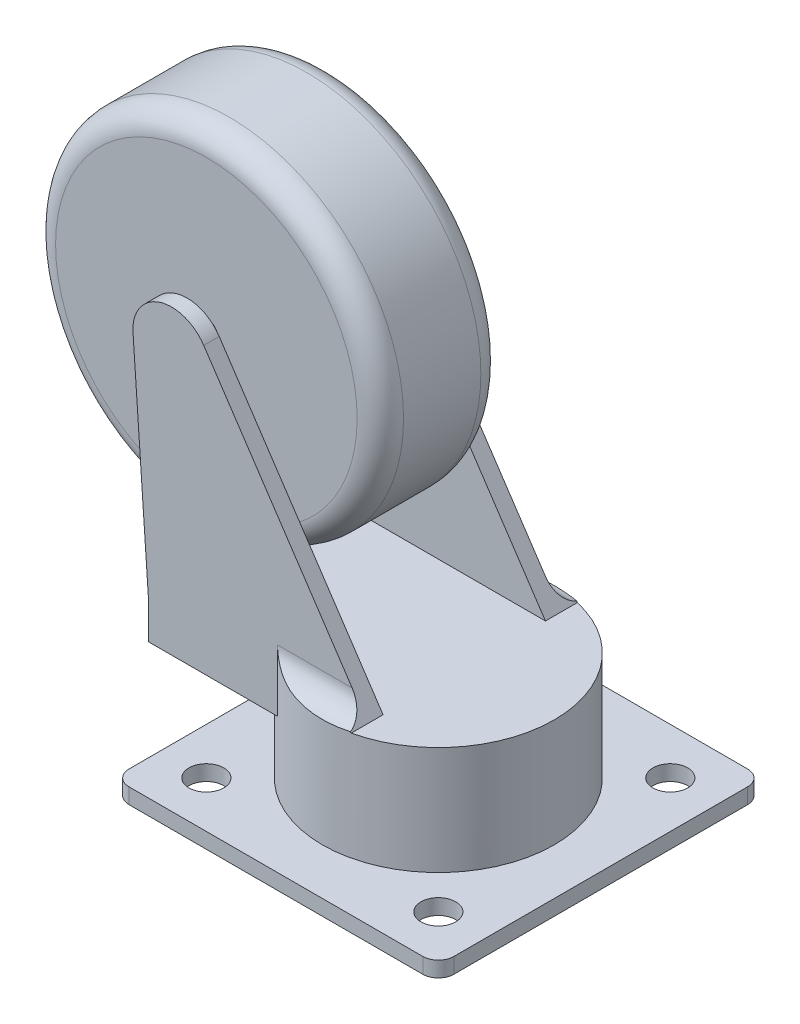
SolidWorks part; units mm, degrees
ref_plane "Front Plane" through (0, 0, 0) normal (0, 0, 1) x (1, 0, 0)
ref_plane "Top Plane" through (0, 0, 0) normal (0, 1, 0) x (1, 0, 0)
ref_plane "Right Plane" through (0, 0, 0) normal (1, 0, 0) x (0, 0, -1)
sketch "Sketch1" plane through (0, 0, 0) normal (0, 1, 0) x (1, 0, 0)
  line L0 (0, 21) -> (0, -21) construction
  line L1 (-19, 21) -> (19, 21)
  line L2 (-21, 19) -> (-21, -19)
  line L3 (-19, -21) -> (19, -21)
  line L4 (21, 19) -> (21, -19)
  line L5 (-21, 21) -> (21, -21) construction
  line L6 (-21, -21) -> (21, 21) construction
  line L7 (-21, 0) -> (21, 0) construction
  circle A0 centre (-15, 15) radius 2.25
  circle A2 centre (15, 15) radius 2.25
  circle A3 centre (15, -15) radius 2.25
  circle A4 centre (-15, -15) radius 2.25
  arc A5 (-21, -19) -> (-19, -21) centre (-19, -19) ccw
  arc A6 (19, -21) -> (21, -19) centre (19, -19) ccw
  arc A7 (19, 21) -> (21, 19) centre (19, 19) cw
  arc A8 (-19, 21) -> (-21, 19) centre (-19, 19) ccw
  point P0 (0, 0)
  dimension "D4" = 2
  dimension "D5" = 4.5
  dimension "D1" = 42
  dimension "D2" = 42
  dimension "D3" = 30
extrude "Boss-Extrude1" add sketch "Sketch1" along normal blind 2
sketch "Sketch2" plane through (0, 2, 0) normal (0, 1, 0) x (1, 0, 0)
  circle A0 centre (0, 0) radius 15
  dimension "D1" = 30
extrude "Boss-Extrude2" add sketch "Sketch2" along normal blind 9
sketch "Sketch3" plane through (0, 11, 0) normal (0, 1, 0) x (1, 0, 0)
  line L0 (0, 0) -> (-36.9933, 0) construction
  line L1 (-25, 12.5) -> (-8.2916, 12.5)
  line L2 (-25, -12.5) -> (-8.2916, -12.5)
  line L3 (-25, 12.5) -> (-25, -12.5)
  circle A0 centre (0, 0) radius 15 construction
  circle A1 centre (0, 0) radius 15 construction
  arc A2 (-8.2916, -12.5) -> (-8.2916, 12.5) centre (0, 0) ccw
  dimension "D1" = 25
  dimension "D2" = 25
extrude "Boss-Extrude3" add sketch "Sketch3" along normal blind 5
sketch "Sketch4" plane through (0, 0, 12.5) normal (0, 0, 1) x (1, 0, 0)
  line L0 (0, 0) -> (0, 48.0736) construction
  line L1 (0, 45) -> (-39.2355, 45) construction
  line L2 (-19, 0) -> (19, 0) construction
  line L3 (-25, 16) -> (-26.988, 44.6539)
  line L4 (3.3542, 16) -> (-17.8405, 47.7746)
  line L5 (15, 16) -> (-8.2916, 16) construction
  line L6 (-25, 16) -> (3.3542, 16)
  circle A0 centre (-22, 45) radius 1.5
  arc A1 (-17.8405, 47.7746) -> (-26.988, 44.6539) centre (-22, 45) ccw
  dimension "D3" = 3
  dimension "D4" = 10
  dimension "D1" = 45
  dimension "D2" = 22
extrude "Boss-Extrude4" add sketch "Sketch4" against normal blind 2
mirror "Mirror1" about plane through (0, 0, 0) normal (0, 0, 1) of "Boss-Extrude4"
fillet "Fillet1" radius 3 2 edges at (-2.4687, 16, -12.5) (-2.4687, 16, 12.5)
sketch "Sketch5" plane through (0, 0, 0) normal (0, 0, 1) x (1, 0, 0)
  circle A0 centre (-22, 45) radius 22.5
  dimension "D1" = 45
extrude "Boss-Extrude5" add sketch "Sketch5" along normal blind 8 and the other way blind 8 separate body
fillet "Fillet2" radius 3 2 edges at (0.5, 45, 8) (0.5, 45, -8)
sketch "Sketch6" plane through (0, 0, 12.5) normal (0, 0, 1) x (1, 0, 0)
  circle A0 centre (-22, 45) radius 1.5
extrude "Boss-Extrude6" add sketch "Sketch6" against normal up to surface (25 mm away) up to face at (-15.8941, 24.5638, -12.5)
